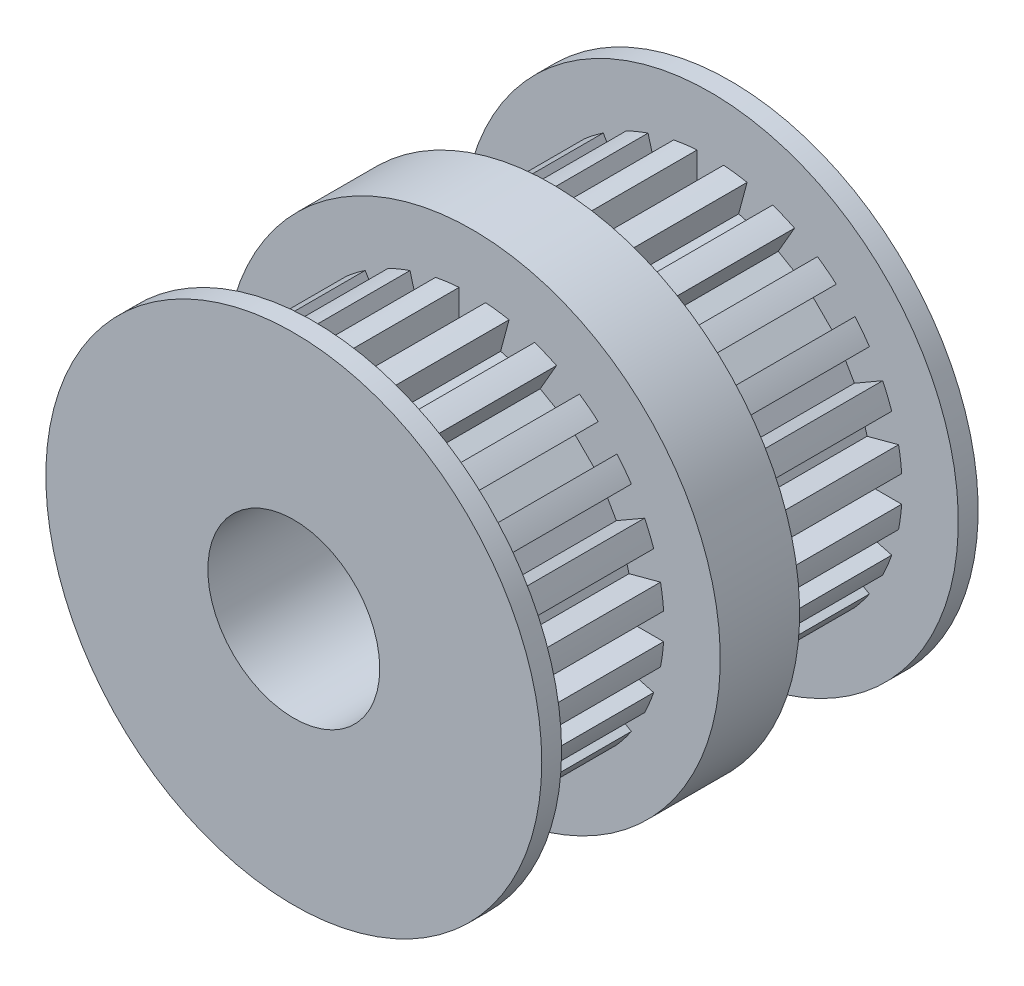
SolidWorks part; units mm, degrees
ref_plane "Front Plane" through (0, 0, 0) normal (0, 0, 1) x (1, 0, 0)
ref_plane "Top Plane" through (0, 0, 0) normal (0, 1, 0) x (1, 0, 0)
ref_plane "Right Plane" through (0, 0, 0) normal (1, 0, 0) x (0, 0, -1)
sketch "Sketch1" plane through (0, 0, 0) normal (0, 0, 1) x (1, 0, 0)
  circle A0 centre (0, 0) radius 9.525
  dimension "D1" = 19.05
extrude "Boss-Extrude1" add sketch "Sketch1" against normal blind 0.762
sketch "Sketch2" plane through (0, 0, -0.762) normal (0, 0, -1) x (-1, 0, 0)
  circle A0 centre (0, 0) radius 7.366
  dimension "D1" = 14.732
extrude "Boss-Extrude2" add sketch "Sketch2" along normal blind 6.096
sketch "Sketch3" plane through (0, 0, -6.858) normal (0, 0, -1) x (-1, 0, 0)
  circle A0 centre (0, 0) radius 9.525
  dimension "D1" = 19.05
extrude "Boss-Extrude3" add sketch "Sketch3" along normal blind 5.334
sketch "Sketch4" plane through (0, 0, 0) normal (0, 0, 1) x (1, 0, 0)
  circle A0 centre (0, 0) radius 3.302
  dimension "D1" = 6.604
extrude "Cut-Extrude1" cut sketch "Sketch4" against normal blind 57.912
ref_plane "Plane2" through (-7.366, 0, 0) normal (-1, 0, 0) x (0, 0, 1)
sketch "Sketch5" plane through (-7.366, 0, 0) normal (-1, 0, 0) x (0, 0, 1)
  line L0 (-6.858, -7.366) -> (-6.858, 7.366) construction
  line L1 (-6.858, 0.508) -> (-0.762, 0.508)
  line L2 (-6.858, 0.508) -> (-6.858, -0.508)
  line L3 (-6.858, -0.508) -> (-0.762, -0.508)
  line L4 (-0.762, 0.508) -> (-0.762, -0.508)
  line L5 (-0.762, 7.366) -> (-0.762, -7.366) construction
  point P8 (-6.858, 0)
  dimension "D1" = 1.016
extrude "Cut-Extrude2" cut sketch "Sketch5" against normal blind 1.27
ref_axis "Axis1" through (0, 0, -12.192) along (0, 0, 1)
pattern_circular "CirPattern1" count 24 over 360 about axis through (0, 0, -12.192) along (0, 0, 1) of "Cut-Extrude2"
sketch "Sketch6" plane through (0, 0, 0) normal (0, 1, 0) x (1, 0, 0)
  line L0 (-9.525, 12.192) -> (-9.525, 6.858) construction
  line L1 (9.525, 12.192) -> (-9.525, 12.192)
  line L2 (9.525, 12.192) -> (9.525, 8.382)
  line L3 (9.525, 8.382) -> (-9.525, 8.382)
  line L4 (-9.525, 12.192) -> (-9.525, 8.382)
  dimension "D1" = 3.81
extrude "Cut-Extrude3" cut sketch "Sketch6" against normal blind 152.4 and the other way blind 152.4
ref_plane "Plane3" through (0, 0, -8.382) normal (0, 0, -1) x (-1, 0, 0)
sketch "Sketch7" plane through (0, 0, -8.382) normal (0, 0, -1) x (-1, 0, 0)
  circle A0 centre (0, 0) radius 9.525
  dimension "D1" = 19.05
extrude "Boss-Extrude4" add sketch "Sketch7" along normal blind 1.524
mirror "Mirror7" about plane through (0, 0, -8.382) normal (0, 0, -1) of "Boss-Extrude2"
mirror "Mirror8" about plane through (0, 0, -8.382) normal (0, 0, -1) of "CirPattern1"
mirror "Mirror9" about plane through (0, 0, -8.382) normal (0, 0, -1) of "Boss-Extrude1"
sketch "Sketch8" plane through (0, 0, -16.764) normal (0, 0, -1) x (-1, 0, 0)
  circle A0 centre (0, 0) radius 3.302
  dimension "D1" = 6.604
extrude "Cut-Extrude4" cut sketch "Sketch8" against normal blind 22.098
